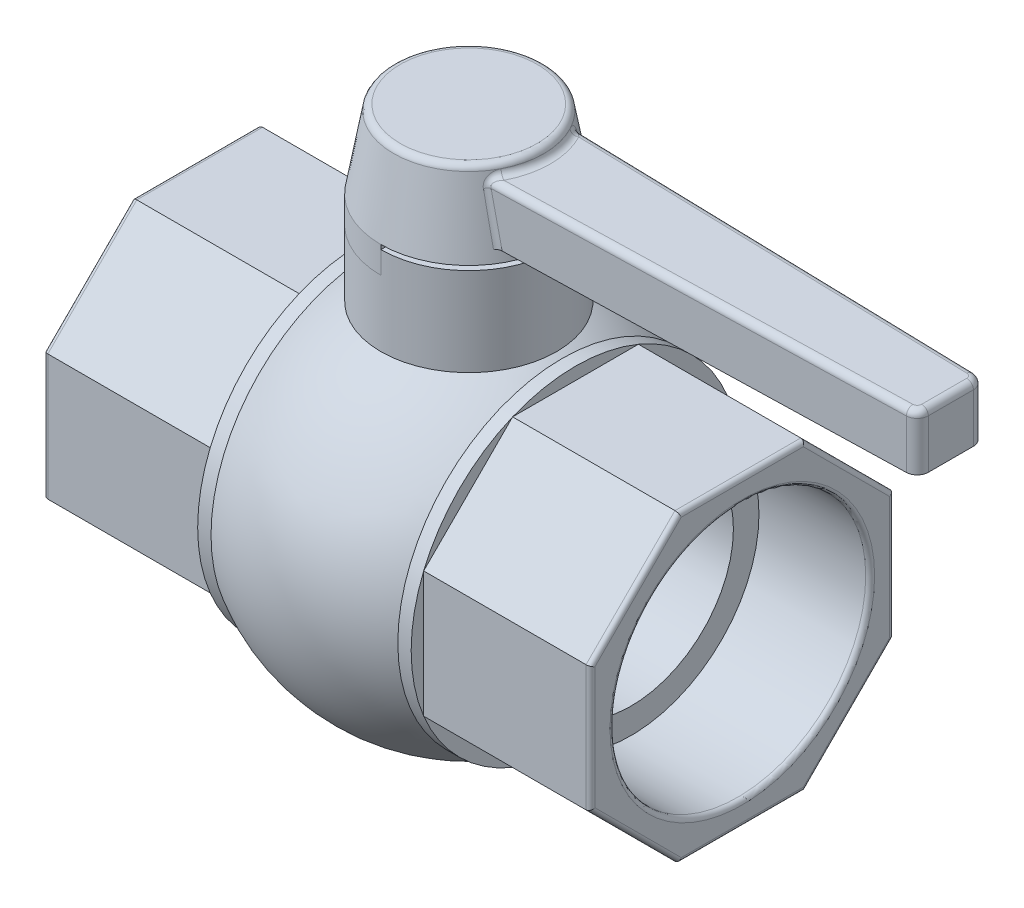
SolidWorks part; units mm, degrees
ref_plane "Front Plane" through (0, 0, 0) normal (0, 0, 1) x (1, 0, 0)
ref_plane "Top Plane" through (0, 0, 0) normal (0, 1, 0) x (1, 0, 0)
ref_plane "Right Plane" through (0, 0, 0) normal (1, 0, 0) x (0, 0, -1)
sketch "Sketch1" plane through (0, 0, 0) normal (0, 0, 1) x (1, 0, 0)
  line L0 (-122.5, 0) -> (122.5, 0) construction
  line L1 (0, 0) -> (0, 85) construction
  line L2 (-42, 73.8986) -> (-42, 0) construction
  line L3 (42, 73.8986) -> (42, 0) construction
  line L4 (42, 73.8986) -> (48, 73.8986)
  line L5 (-42, 73.8986) -> (-48, 73.8986)
  line L6 (-48, 73.8986) -> (-48, 36)
  line L7 (48, 73.8986) -> (48, 36)
  arc A0 (42, 73.8986) -> (-42, 73.8986) centre (0, 0) ccw
  arc A1 (48, 36) -> (-48, 36) centre (0, 0) ccw
  dimension "D2" = 170
  dimension "D5" = 120
  dimension "D1" = 245
  dimension "D3" = 42
  dimension "D4" = 6
revolve "Revolve1" add sketch "Sketch1" angle 360 about L0
sketch "Sketch2" plane through (48, 0, 0) normal (1, 0, 0) x (0, 0, -1)
  line L1 (28.2798, 68.2734) -> (-28.2798, 68.2734)
  line L2 (-28.2798, 68.2734) -> (-68.2734, 28.2798)
  line L3 (-68.2734, 28.2798) -> (-68.2734, -28.2798)
  line L4 (-68.2734, -28.2798) -> (-28.2798, -68.2734)
  line L5 (-28.2798, -68.2734) -> (28.2798, -68.2734)
  line L6 (28.2798, -68.2734) -> (68.2734, -28.2798)
  line L7 (68.2734, -28.2798) -> (68.2734, 28.2798)
  line L8 (68.2734, 28.2798) -> (28.2798, 68.2734)
  circle A0 centre (0, 0) radius 68.2734 construction
  circle A1 centre (0, 0) radius 46
  dimension "D1" = 92
extrude "Boss-Extrude1" add sketch "Sketch2" along normal blind 75
sketch "Sketch3" plane through (123, 0, 0) normal (1, 0, 0) x (0, 0, -1)
  circle A0 centre (0, 0) radius 57.5
  dimension "D1" = 115
extrude "Cut-Extrude1" cut sketch "Sketch3" against normal blind 50
mirror "Mirror1" about plane through (0, 0, 0) normal (1, 0, 0) of "Cut-Extrude1", "Boss-Extrude1"
ref_plane "Plane1" through (0, 115, 0) normal (0, 1, 0) x (1, 0, 0)
sketch "Sketch4" plane through (0, 115, 0) normal (0, 1, 0) x (1, 0, 0)
  circle A0 centre (0, 0) radius 39.5
  dimension "D1" = 79
extrude "Boss-Extrude2" add sketch "Sketch4" against normal up to surface (39.7355 mm away) up to face at (-42, 0, 73.8986)
sketch "Sketch5" plane through (0, 115, 0) normal (0, 1, 0) x (1, 0, 0)
  circle A0 centre (0, 0) radius 27.5
  dimension "D1" = 55
extrude "Cut-Extrude2" cut sketch "Sketch5" against normal through all both and the other way through all
sketch "Sketch6" plane through (0, 115, 0) normal (0, 1, 0) x (1, 0, 0)
  line L0 (0, 0) -> (0, -39.5)
  line L1 (0, 0) -> (39.5, 0)
  arc A0 (39.5, 0) -> (0, -39.5) centre (0, 0) ccw
extrude "Cut-Extrude3" cut sketch "Sketch6" against normal blind 10
sketch "Sketch7" plane through (0, 105, 0) normal (0, 1, 0) x (1, 0, 0)
  line L2 (27.5, 0) -> (39.5, 0)
  line L3 (0, -39.5) -> (0, -27.5)
  line L4 (27.5, 0) -> (39.5, 0)
  line L5 (0, -39.5) -> (0, -27.5)
  arc A2 (27.5, 0) -> (0, -27.5) centre (0, 0) ccw
  arc A3 (39.5, 0) -> (0, -39.5) centre (0, 0) ccw
  arc A4 (27.5, 0) -> (0, -27.5) centre (0, 0) ccw
  arc A5 (39.5, 0) -> (0, -39.5) centre (0, 0) ccw
  dimension "D1" = 0
extrude "Boss-Extrude3" add sketch "Sketch7" along normal blind 12 separate body
sketch "Sketch8" plane through (0, 117, 0) normal (0, 1, 0) x (1, 0, 0)
  circle A0 centre (0, 0) radius 39.5
extrude "Boss-Extrude4" add sketch "Sketch8" along normal blind 35 draft 10
sketch "Sketch9" plane through (0, 152, 0) normal (0, 1, 0) x (1, 0, 0)
  line L0 (26.6607, 0) -> (216.794, 0) construction
  line L1 (26.6607, 20) -> (216.794, 15)
  line L3 (26.6607, -20) -> (216.794, -15)
  line L4 (216.794, 15) -> (216.794, -15)
  line L5 (26.6607, 20) -> (26.6607, -20) construction
  circle A0 centre (0, 0) radius 33.3286 construction
  arc A1 (26.6607, 20) -> (26.6607, -20) centre (0, 0) cw
  dimension "D1" = 30
  dimension "D2" = 40
extrude "Boss-Extrude5" add sketch "Sketch9" against normal blind 25 from offset 5 offset against normal yes
fillet "Fillet1" radius 5 2 edges at (216.794, 134.5, -15) (216.794, 134.5, 15)
fillet "Fillet2" radius 3 1 edges at (0, 152, 33.3286)
fillet "Fillet3" radius 3 8 edges at (215.3757, 147, 13.6185) (119.8507, 147, 17.5493) (34.2102, 147, 0) (119.8507, 147, -17.5493) (215.3757, 147, -13.6185) (216.794, 147, 0)
fillet "Fillet4" radius 2 18 edges at (123, 0, -68.2734) (123, -48.2766, -48.2766) (123, -68.2734, 0) (123, -48.2766, 48.2766) (123, 0, 68.2734) (123, 48.2766, 48.2766) (123, 68.2734, 0) (123, 48.2766, -48.2766) (123, 0, -57.5) (-123, 68.2734, 0) (-123, 48.2766, 48.2766) (-123, 0, 68.2734) (-123, -48.2766, 48.2766) (-123, -68.2734, 0) (-123, -48.2766, -48.2766) (-123, 0, -68.2734) (-123, 48.2766, -48.2766) (-123, 0, -57.5)
other "CPoint1" parameters "Diameter"=101.6, "StubLength"=76.2
ref_axis "Axis1" through (-83, 0, 0) along (1, 0, 0)
other "CPoint2" parameters "Diameter"=101.6, "StubLength"=152.4
ref_axis "Axis2" through (83, 0, 0) along (-1, 0, 0)
other "RPoint1"
ref_axis "Vertical" through (0, 0, 0) along (0, 1, 0)
